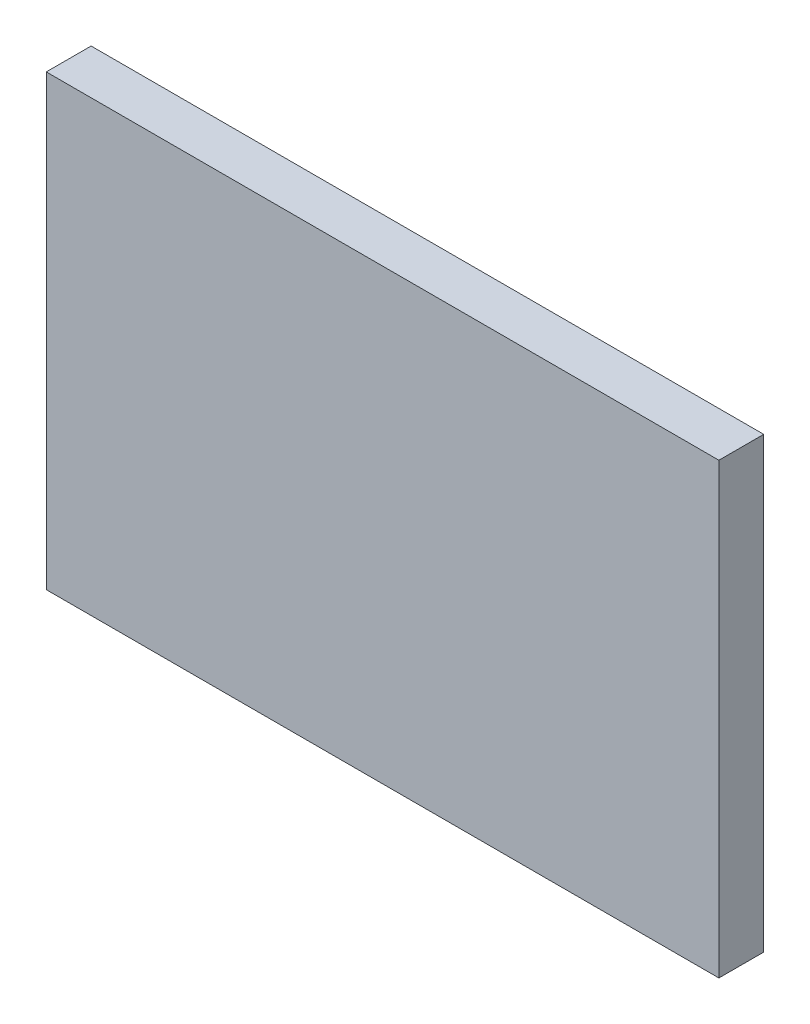
SolidWorks part; units mm, degrees
ref_plane "Ebene vorne" through (0, 0, 0) normal (0, 0, 1) x (1, 0, 0)
ref_plane "Ebene oben" through (0, 0, 0) normal (0, 1, 0) x (1, 0, 0)
ref_plane "Ebene rechts" through (0, 0, 0) normal (1, 0, 0) x (0, 0, -1)
sketch "Skizze1" plane through (0, 0, 0) normal (0, 0, 1) x (1, 0, 0)
  line L0 (0, 0) -> (0, 20)
  line L1 (0, 20) -> (30, 20)
  line L2 (30, 20) -> (30, 0)
  line L3 (30, 0) -> (0, 0)
  dimension "D1" = 30
  dimension "D2" = 20
  dimension "D3" = 20
  dimension "D4" = 90
  dimension "D5" = 90
extrude "Aufsatz-Linear austragen1" add sketch "Skizze1" along normal blind 2
sketch "Skizze4" plane through (0, 0, 0) normal (0, 0, 1) x (1, 0, 0)
  line L1 (0, 0) -> (30, 0)
  line L2 (0, 0) -> (0, 20)
  line L3 (0, 20) -> (30, 20)
  line L4 (30, 0) -> (30, 20)
  dimension "D1" = 30
  dimension "D2" = 20
sketch "Skizze2" plane through (0, 0, 2) normal (0, 0, 1) x (1, 0, 0)
  circle A0 centre (15, 10) radius 18.0278
sketch "Skizze3" plane through (0, 0, 2) normal (0, 0, 1) x (1, 0, 0)
  line L0 (1, 1) -> (29, 1)
  line L1 (1, 1) -> (1, 19)
  line L2 (29, 1) -> (29, 19)
  line L3 (1, 19) -> (29, 19)
  line L4 (1, 1) -> (29, 19) construction
  line L5 (29, 1) -> (1, 19) construction
  line L6 (30, 0) -> (30, 20) construction
  line L7 (30, 20) -> (0, 20) construction
  point P1 (15, 10)
  point P8 (30, 10)
  point P11 (15, 20)
  dimension "D1" = 18
  dimension "D2" = 28
ref_point "SWASI_Vision_Point_1"
ref_point "SWASI_Vision_Point_1_helper"
ref_point "SWASI_Vision_Point_2"
ref_point "SWASI_Vision_Point_2_helper"
ref_point "SWASI_Vision_Point_3"
ref_point "SWASI_Vision_Point_3_helper"
ref_point "SWASI_Vision_Point_4"
ref_plane "SWASI_Alignment_Plane_1" through (0, 0, 0) normal (0, -1, 0) x (-1, 0, 0)
ref_plane "SWASI_Alignment_Plane_2ddasd" through (0, 0, 0) normal (0, 0, 1) x (1, 0, 0)
ref_axis "Achse1" through (30, 0, 2) along (-1, 0, 0)
ref_axis "Achse2" through (0, 0, 2) along (0.9978, 0, -0.0665)
ref_axis "Achse3" through (0, 0, 0) along (0.9978, 0, 0.0665)
ref_point "SWASI_Surface_Center_Point"
ref_axis "Achse5" through (0, 0, 2) along (0, 0, -1)
ref_axis "SWASI_Norm_Alignment_Plane_3" through (30, 0, 0) along (-1, 0, 0)
ref_plane "SWASI_Alignment_Plane_3" through (15, 0, 1) normal (-1, 0, 0) x (0, 0, 1)
ref_point "Punkt1"
ref_point "Punkt2"
